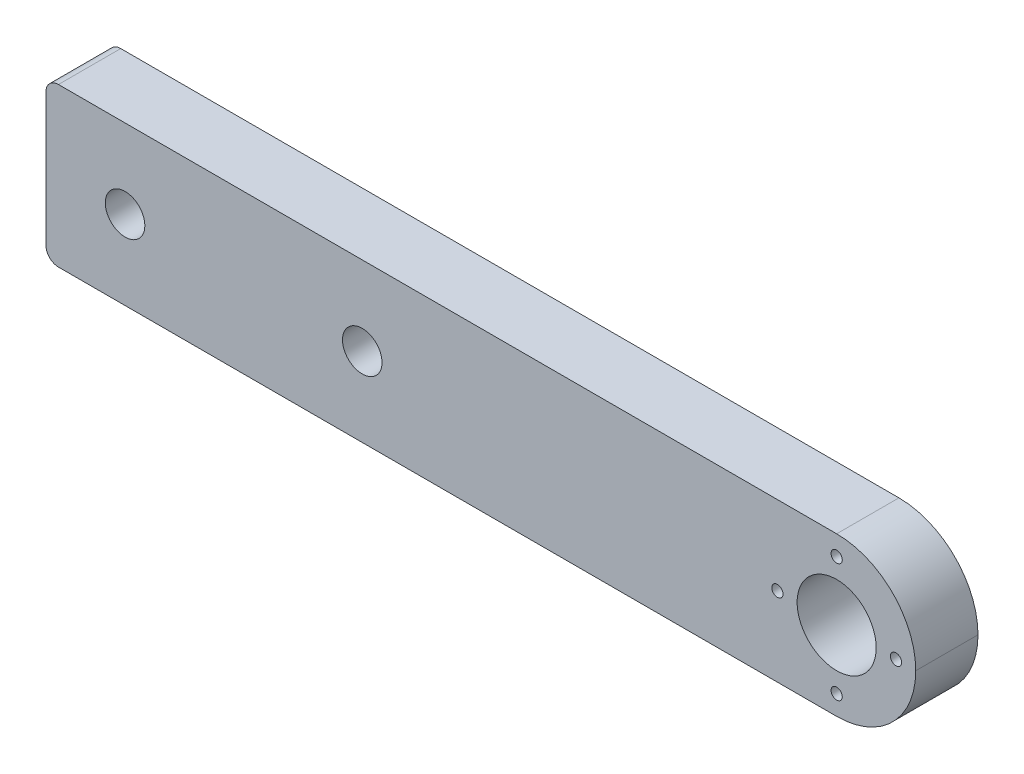
SolidWorks part; units mm, degrees
ref_plane "Front Plane" through (0, 0, 0) normal (0, 0, 1) x (1, 0, 0)
ref_plane "Top Plane" through (0, 0, 0) normal (0, 1, 0) x (1, 0, 0)
ref_plane "Right Plane" through (0, 0, 0) normal (1, 0, 0) x (0, 0, -1)
sketch "Sketch1" plane through (0, 0, 0) normal (0, 0, 1) x (1, 0, 0)
  line L0 (-50.8, 0) -> (-63.5, 0) construction
  line L2 (-63.5, -12.7) -> (-63.5, 12.7)
  line L4 (63.5, -12.7) -> (63.5, 12.7) construction
  line L5 (-63.5, -12.7) -> (63.5, 12.7) construction
  line L6 (-63.5, 12.7) -> (63.5, -12.7) construction
  line L12 (63.5, 9.525) -> (63.5, -9.525) construction
  line L18 (53.975, 0) -> (73.025, 0) construction
  line L19 (-50.8, 0) -> (-12.7, 0) construction
  line L20 (63.5, -12.7) -> (-63.5, -12.7)
  line L21 (63.5, 12.7) -> (-63.5, 12.7)
  line L22 (63.5, -12.7) -> (76.2, -12.7)
  line L23 (76.2, -12.7) -> (76.2, 12.7)
  line L24 (76.2, 12.7) -> (63.5, 12.7)
  circle A0 centre (-50.8, 0) radius 3.175
  circle A6 centre (63.5, 0) radius 6.35
  circle A8 centre (63.5, 9.525) radius 0.9
  circle A9 centre (63.5, -9.525) radius 0.9
  circle A10 centre (53.975, 0) radius 0.9
  circle A11 centre (73.025, 0) radius 0.9
  circle A12 centre (-12.7, 0) radius 3.175
  point P0 (0, 0)
  point P23 (63.5, 0)
  point P24 (63.5, 0)
  dimension "D4" = 6.35
  dimension "D7" = 1.8
  dimension "D8" = 12.7
  dimension "D10" = 19.05
  dimension "D2" = 76.2
  dimension "D3" = 12.7
  dimension "D5" = 139.7
  dimension "D9" = 19.05
  dimension "D12" = 38.1
  dimension "D13" = 25.4
  dimension "D14" = 12.7
extrude "Boss-Extrude1" add sketch "Sketch1" along normal blind 10
fillet "Fillet2" radius 2 2 edges at (-63.5, -12.7, 5) (-63.5, 12.7, 5)
fillet "Fillet3" radius 12.7 2 edges at (76.2, 12.7, 5) (76.2, -12.7, 5)
